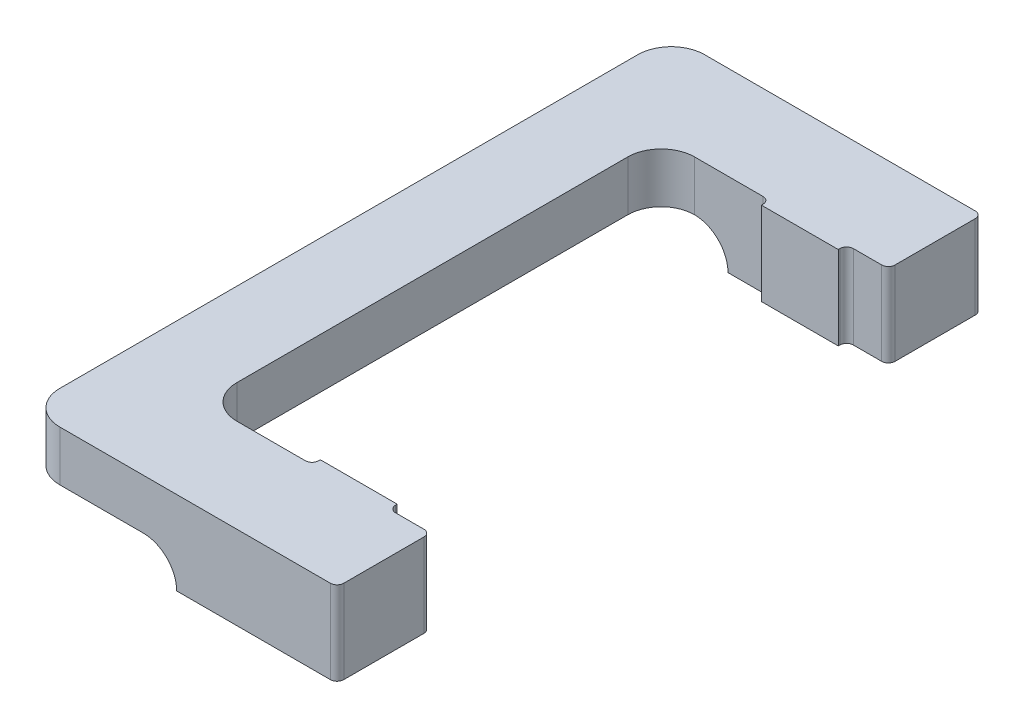
SolidWorks part; units mm, degrees
ref_plane "Front" through (0, 0, 0) normal (0, 0, 1) x (1, 0, 0)
ref_plane "Top" through (0, 0, 0) normal (0, 1, 0) x (1, 0, 0)
ref_plane "Right" through (0, 0, 0) normal (1, 0, 0) x (0, 0, -1)
sketch "Эскиз1" plane through (0, 0, 0) normal (0, 1, 0) x (1, 0, 0)
  line L0 (4.7471, 19.587) -> (-3.2529, 19.587)
  line L1 (4.7471, 19.587) -> (4.7471, 15.587)
  line L2 (4.7471, 15.587) -> (2.2471, 15.587)
  line L3 (-3.2529, 19.587) -> (-3.2529, 15.587)
  line L4 (4.7471, -13.413) -> (2.2471, -13.413)
  line L5 (4.7471, -13.413) -> (4.7471, -17.413)
  line L6 (4.7471, -17.413) -> (-3.2529, -17.413)
  line L7 (-3.2529, -13.413) -> (-3.2529, -17.413)
  line L8 (-0.7529, 15.587) -> (-3.2529, 15.587)
  line L10 (-0.7529, 15.587) -> (-0.7529, 15.087)
  line L11 (-0.7529, 15.087) -> (2.2471, 15.087)
  line L12 (2.2471, 15.587) -> (2.2471, 15.087)
  line L13 (0.7471, 19.587) -> (0.7471, -17.413) construction
  line L14 (0.7471, 1.087) -> (17.1648, 1.087) construction
  line L15 (2.2471, -13.413) -> (2.2471, -12.913)
  line L16 (-0.7529, -12.913) -> (2.2471, -12.913)
  line L17 (-0.7529, -13.413) -> (-0.7529, -12.913)
  line L18 (-0.7529, -13.413) -> (-3.2529, -13.413)
  point P8 (0.7471, 15.587)
  dimension "D1" = 8
  dimension "D3" = 3
extrude "Вытянуть-Тонкостенный1" add sketch "Эскиз1" along normal blind 5 thin thin type one direction wall 0.8
sketch "Эскиз2" plane through (0, 5, 0) normal (0, 1, 0) x (1, 0, 0)
  line L0 (-4.0529, 20.387) -> (-13.0529, 20.387)
  line L1 (-13.0529, 20.387) -> (-13.0529, -18.213)
  line L2 (-13.0529, -18.213) -> (-4.0529, -18.213)
  line L3 (-4.0529, -18.213) -> (-4.0529, -12.613)
  line L4 (-4.0529, -12.613) -> (-8.0529, -12.613)
  line L5 (-8.0529, -12.613) -> (-8.0529, 14.787)
  line L6 (-8.0529, 14.787) -> (-4.0529, 14.787)
  line L7 (-4.0529, 14.787) -> (-4.0529, 20.387)
  line L8 (-4.0529, 14.787) -> (-1.5529, 14.787) construction
  line L9 (-1.5529, -12.613) -> (-4.0529, -12.613) construction
  point P3 (0, 0)
  point P13 (0, 0)
  point P14 (0, 0)
  point P15 (-4.0529, 14.787)
  point P18 (0, 0)
  point P19 (0, 0)
  point P20 (-4.0529, -12.613)
  dimension "D1" = 5
  dimension "D2" = 9
extrude "Бобышка-Вытянуть1" add sketch "Эскиз2" against normal blind 3
sketch "Эскиз3" plane through (0, 5, 0) normal (0, 1, 0) x (1, 0, 0)
  line L1 (-3.2529, 19.587) -> (4.7471, 19.587)
  line L2 (-3.2529, 19.587) -> (-3.2529, 15.087)
  line L3 (-3.2529, 15.087) -> (4.7471, 15.087)
  line L4 (4.7471, 19.587) -> (4.7471, 15.087)
  line L5 (-3.2529, -12.913) -> (4.7471, -12.913)
  line L6 (-3.2529, -12.913) -> (-3.2529, -17.413)
  line L7 (-3.2529, -17.413) -> (4.7471, -17.413)
  line L8 (4.7471, -12.913) -> (4.7471, -17.413)
  point P12 (0, 0)
  point P13 (0, 0)
  point P14 (0, 0)
  point P15 (0, 0)
  point P16 (4.7471, 15.087)
  point P17 (0, 0)
  point P18 (-3.2529, -12.913)
extrude "Бобышка-Вытянуть2" add sketch "Эскиз3" against normal blind 1
fillet "Скругление1" radius 2 6 edges at (-4.0529, 2, -17.587) (-4.0529, 2, 15.413) (-8.0529, 3.5, 12.613) (-8.0529, 3.5, -14.787) (-13.0529, 3.5, -20.387) (-13.0529, 3.5, 18.213)
fillet "Скругление2" radius 0.4 4 edges at (5.5471, 2.5, -20.387) (5.5471, 2.5, -14.787) (5.5471, 2.5, 12.613) (5.5471, 2.5, 18.213)
fillet "Скругление3" radius 0.4 8 edges at (3.0471, 2.5, 12.613) (-1.5529, 2.5, 12.613) (-0.7529, 2, 13.413) (2.2471, 2, 13.413) (3.0471, 2.5, -14.787) (-1.5529, 2.5, -14.787) (2.2471, 2, -15.587) (-0.7529, 2, -15.587)
